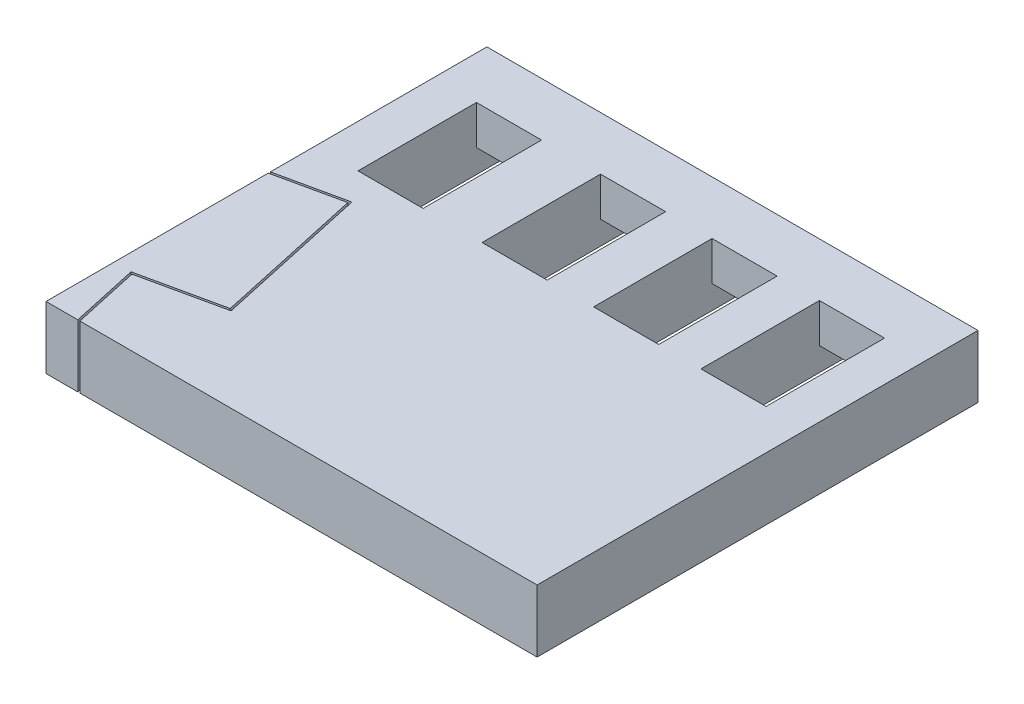
SolidWorks part; units mm, degrees
ref_plane "Front Plane" through (0, 0, 0) normal (0, 0, 1) x (1, 0, 0)
ref_plane "Top Plane" through (0, 0, 0) normal (0, 1, 0) x (1, 0, 0)
ref_plane "Right Plane" through (0, 0, 0) normal (1, 0, 0) x (0, 0, -1)
sketch "Sketch2" plane through (0, 0, 0) normal (0, 1, 0) x (1, 0, 0)
  line L0 (-9.37, 7.32) -> (73.63, 7.32) construction
  line L1 (73.63, 7.32) -> (76.4595, -28.3475) construction
  line L2 (76.4595, -28.3475) -> (60, -92.68) construction
  line L3 (60, -92.68) -> (0, -92.68) construction
  line L4 (0, -92.68) -> (-14.4952, -26.391) construction
  line L5 (-14.4952, -26.391) -> (-9.37, 7.32) construction
  line L6 (0, -92.68) -> (0, 7.32) construction
  line L7 (0, -92.68) -> (-39.3219, -55.4519) construction
  line L8 (-39.3219, -55.4519) -> (-24.668, -37.068) construction
  line L9 (-24.668, -37.068) -> (-14.4952, -26.391) construction
  line L10 (23.833, 7.32) -> (23.833, -92.68) construction
  line L11 (45.253, 7.32) -> (45.253, -92.68) construction
  line L12 (65.8765, 7.32) -> (65.8765, -69.7116) construction
  line L13 (75.6226, -17.7975) -> (-13.1887, -17.7975) construction
  line L14 (-9.3242, -50.0388) -> (70.9098, -50.0388) construction
  line L15 (-9.37, 7.32) -> (9.37, 7.32)
  line L16 (73.63, 7.32) -> (58.123, 7.32)
  line L17 (58.123, 7.32) -> (65.8765, 7.32)
  line L18 (35.883, 7.32) -> (54.623, 7.32)
  line L19 (14.463, 7.32) -> (33.203, 7.32)
  line L20 (21.0829, 0) -> (43.1082, 0) construction
  spline S0 degree 3 poles (-24.668, -37.068) (-25.0537, -36.7059) (-25.7619, -36.0411) (-26.7353, -35.1295) (-28.0424, -33.9071) (-29.2031, -32.8245) (-30.7142, -31.418) (-32.1196, -30.112) (-34.552, -27.8566) (-36.7318, -25.839) (-39.4542, -23.3171) (-41.6352, -21.2933) (-44.115, -18.9831) (-45.906, -17.309) (-47.5157, -15.8001) (-48.9606, -14.444) (-50.2857, -13.2006) (-51.3935, -12.1603) (-52.3511, -11.2593) (-53.3729, -10.2955) (-54.4927, -9.2355) (-55.8015, -7.9921) (-56.6965, -7.137) (-57.2305, -6.6269) knots 0 0 0 0 0.035582 0.065325 0.089678 0.15593 0.172056 0.228511 0.284969 0.395211 0.428397 0.534723 0.595442 0.656419 0.699627 0.743832 0.789646 0.821914 0.846336 0.87839 0.916737 0.950329 1 1 1 1 construction
  point P21 (0, 7.32)
  point P22 (65.8765, 0)
  point P28 (45.253, 7.32)
  point P31 (23.833, 7.32)
  point P32 (45.253, 0)
  point P33 (23.833, 0)
  dimension "D1" = 83
  dimension "D2" = 100
  dimension "D3" = 60
  dimension "D4" = 18.74
  dimension "D5" = 7.7535
  dimension "D6" = 10.55
  dimension "D7" = 18.74
  dimension "D8" = 18.74
  dimension "D9" = 3.5
  dimension "D10" = 2.68
ref_plane "Plane1" through (0, 0, -7.32) normal (0, 0, 1) x (1, 0, 0)
ref_plane "Plane2" through (0, 0, 92.68) normal (0, 0, -1) x (-1, 0, 0)
ref_plane "Plane jari tengah" through (23.833, 0, 0) normal (-1, 0, 0) x (0, 0, 1)
ref_plane "Plane telunjuk" through (0, 0, 0) normal (1, 0, 0) x (0, 0, -1)
ref_plane "Plane Jari MANIS" through (45.253, 0, 0) normal (-1, 0, 0) x (0, 0, 1)
ref_plane "Plane KELINGKING" through (65.8765, 0, 0) normal (-1, 0, 0) x (0, 0, 1)
sketch "Sketch8" plane through (0, 0, 92.68) normal (0, 0, -1) x (-1, 0, 0)
  line L0 (-60, 0) -> (0, 0) construction
  ellipse E0 centre (-30, 0) end of major axis (-60, 0) minor radius 14
  point P9 (-30, 0)
  dimension "D1" = 28
sketch "SK tengah" plane through (23.833, 0, 0) normal (-1, 0, 0) x (0, 0, 1)
  line L0 (-7.32, 9.9745) -> (0.9825, 14.5812) construction
  line L1 (0.9825, 14.5812) -> (92.68, 14.5812) construction
  line L2 (92.68, 14.5812) -> (92.68, -18.4188) construction
  line L3 (92.68, -18.4188) -> (-7.32, -18.4188) construction
  line L4 (-7.32, -18.4188) -> (-7.32, 9.9745) construction
  line L5 (25.1136, 0) -> (25.1136, 14.5812) construction
  line L6 (-7.32, 0) -> (92.68, 0) construction
  line L7 (25.1136, 0) -> (25.1136, -18.4188) construction
  line L8 (11.0531, -18.4188) -> (26.0531, -18.4188)
  line L9 (13.6136, 14.5812) -> (36.6136, 14.5812) construction
  point P3 (0, 0)
  point P21 (18.5531, -18.4188)
  point P23 (25.1136, 14.5812)
  dimension "D1" = 33
  dimension "D2" = 23
  dimension "D3" = 15
sketch "Sketch T tengah" plane through (23.833, 0, 0) normal (-1, 0, 0) x (0, 0, 1)
  line L1 (-7.32, -18.4188) -> (-7.32, 9.9745) construction
  line L3 (-7.72, -8.3628) -> (0.6719, -4.4495) construction
  spline S0 degree 1 poles (36.6136, 14.5812) (92.68, 13.701) knots 0 0 1 1
  spline S1 degree 3 poles (11.0531, -18.4188) (2.4609, -15.2512) (-3.4722, -11.6219) (-7.32, -8.1763) knots 0 0 0 0 1 1 1 1
  spline S2 degree 3 poles (26.0531, -18.4188) (48.3054, -13.7834) (72.3805, -31.2632) (92.68, -13.701) knots 0 0 0 0 1 1 1 1
  spline S3 degree 2 poles (13.6136, 14.5812) (4.5745, 14.3991) (-7.32, 5.7198) knots 0 0 0 1 1 1
  spline S4 degree 2 poles (11.0531, -18.4188) (19.1579, -19.8516) (26.9692, -18.2405) knots 0 0 0 1 1 1
  spline S5 degree 3 poles (13.6136, 14.5812) (23.8468, 14.7873) (29.5425, 14.6922) (37.7057, 14.5641) knots 0 0 0 0 1 1 1 1
sketch "Sketch T Telunjuk" plane through (0, 0, 0) normal (1, 0, 0) x (0, 0, -1)
  line L0 (-92.68, 14.5812) -> (-92.68, -18.4188) construction
  line L1 (-92.68, -18.4188) -> (7.32, -18.4188) construction
  line L2 (7.32, -18.4188) -> (7.32, 9.9745) construction
  line L3 (-0.9825, 14.5812) -> (-92.68, 14.5812) construction
  line L4 (7.32, 9.9745) -> (-0.9825, 14.5812) construction
  line L5 (-11.0531, -18.4188) -> (-26.0531, -18.4188) construction
  line L6 (-25.1136, 0) -> (-25.1136, -18.4188) construction
  line L7 (-13.6136, 14.5812) -> (-36.6136, 14.5812) construction
  line L8 (-25.1136, 0) -> (-25.1136, 14.5812) construction
  line L9 (-92.68, 14.5812) -> (-92.68, -18.4188) construction
  line L10 (-92.68, -18.4188) -> (7.32, -18.4188) construction
  line L11 (7.32, -18.4188) -> (7.32, 9.9745) construction
  line L12 (-0.9825, 14.5812) -> (-92.68, 14.5812) construction
  line L13 (7.32, 9.9745) -> (-0.9825, 14.5812) construction
  line L14 (-11.0531, -18.4188) -> (-26.0531, -18.4188)
  line L15 (-25.1136, 0) -> (-25.1136, -18.4188) construction
  line L16 (-13.6136, 14.5812) -> (-36.6136, 14.5812)
  line L17 (-25.1136, 0) -> (-25.1136, 14.5812) construction
  line L19 (-14, 6.5) -> (-18, 6.5) construction
  line L22 (-92.68, 2.3377) -> (-92.68, -9.5106) construction
  spline S0 degree 2 poles (-13.6136, 14.5812) (-1.7806, 13.7761) (7.32, 6.5) knots 0 0 0 1 1 1
  spline S1 degree 3 poles (-36.6136, 14.5812) (-55.7606, 12.6324) (-92.68, 8.8052) (-92.68, 0) knots 0 0 0 0 1 1 1 1
  spline S2 degree 2 poles (7.32, -9.651) (-1.1831, -15.409) (-11.0531, -18.4188) knots 0 0 0 1 1 1
  spline S3 degree 3 poles (-26.0531, -18.4188) (-34.8378, -16.2128) (-50.5034, -20.7443) (-75.8269, -26.8447) (-92.68, -20.3045) (-92.68, 0) knots 0 0 0 0 0.475651 0.575651 1 1 1 1
  spline S4 degree 2 poles (-11.0531, -18.4188) (-19.9341, -19.78) (-28.5243, -17.9627) knots 0 0 0 1 1 1
  spline S5 degree 2 poles (-36.6136, 14.5812) (-23.4423, 15.8073) (-10.4204, 14.2388) knots 0 0 0 1 1 1
  point P14 (0, 0)
sketch "Sketch T manis" plane through (45.253, 0, 0) normal (-1, 0, 0) x (0, 0, 1)
  line L0 (13.6136, 14.5812) -> (36.6136, 14.5812) construction
  line L1 (11.0531, -18.4188) -> (26.0531, -18.4188) construction
  line L2 (-7.32, 9.9745) -> (0.9825, 14.5812) construction
  line L3 (25.1136, 0) -> (25.1136, -18.4188) construction
  line L4 (25.1136, 0) -> (25.1136, 14.5812) construction
  line L5 (-7.32, -18.4188) -> (-7.32, 9.9745) construction
  line L6 (92.68, -18.4188) -> (-7.32, -18.4188) construction
  line L7 (92.68, 14.5812) -> (92.68, -18.4188) construction
  line L8 (0.9825, 14.5812) -> (92.68, 14.5812) construction
  line L9 (13.6136, 14.5812) -> (36.6136, 14.5812) construction
  line L10 (11.0531, -18.4188) -> (26.0531, -18.4188)
  line L11 (-7.32, 9.9745) -> (0.9825, 14.5812) construction
  line L12 (25.1136, 0) -> (25.1136, -18.4188)
  line L13 (25.1136, 0) -> (25.1136, 14.5812)
  line L14 (-7.32, -18.4188) -> (-7.32, 9.9745) construction
  line L15 (92.68, -18.4188) -> (-7.32, -18.4188) construction
  line L16 (92.68, 14.5812) -> (92.68, -18.4188) construction
  line L17 (0.9825, 14.5812) -> (92.68, 14.5812) construction
  line L18 (30.3671, 14.6142) -> (43.0115, 14.5474) construction
  spline S0 degree 2 poles (-7.32, -12.0108) (1.4272, -16.457) (11.0531, -18.4188) knots 0 0 0 1 1 1
  spline S1 degree 1 poles (11.0531, -18.4188) (26.0531, -18.4188) knots 0 0 1 1
  spline S2 degree 1 poles (11.0531, -18.4188) (26.0531, -18.4188) knots 0 0 1 1
  spline S3 degree 2 poles (-7.32, 5.7198) (2.2712, 12.9568) (13.6136, 14.5812) knots 0 0 0 1 1 1
  spline S4 degree 3 poles (36.6136, 14.5812) (55.2526, 14.4826) (74.0747, 13.0063) (92.68, 12.0554) knots 0 0 0 0 1 1 1 1
  spline S5 degree 3 poles (26.0531, -18.4188) (37.9494, -16.5166) (59.1128, -17.1776) (83.6124, -25.345) (92.68, -12.0554) knots 0 0 0 0 0.46971 1 1 1 1
  spline S6 degree 3 poles (26.0531, -18.4188) (48.3054, -13.7834) (72.3805, -31.2632) (92.68, -13.701) knots 0 0 0 0 1 1 1 1 construction
  spline S7 degree 2 poles (11.0531, -18.4188) (19.948, -19.5169) (28.6529, -18.034) knots 0 0 0 1 1 1
  spline S8 degree 3 poles (36.6136, 14.5812) (28.6207, 14.6235) (16.5345, 16.1804) (7.5854, 13.2859) knots 0 0 0 0 1 1 1 1
sketch "Sketch T kelingking" plane through (65.8765, 0, 0) normal (-1, 0, 0) x (0, 0, 1)
  line L0 (13.6136, 14.5812) -> (36.6136, 14.5812) construction
  line L1 (11.0531, -18.4188) -> (26.0531, -18.4188) construction
  line L2 (-7.32, 9.9745) -> (0.9825, 14.5812) construction
  line L3 (-7.32, -18.4188) -> (-7.32, 9.9745) construction
  line L4 (92.68, -18.4188) -> (-7.32, -18.4188) construction
  line L5 (92.68, 14.5812) -> (92.68, -18.4188) construction
  line L6 (0.9825, 14.5812) -> (92.68, 14.5812) construction
  line L7 (13.6136, 14.5812) -> (36.6136, 14.5812) construction
  line L8 (11.0531, -18.4188) -> (26.0531, -18.4188) construction
  line L9 (-7.32, 9.9745) -> (0.9825, 14.5812) construction
  line L10 (-7.32, -18.4188) -> (-7.32, 9.9745) construction
  line L11 (92.68, -18.4188) -> (-7.32, -18.4188) construction
  line L12 (92.68, 14.5812) -> (92.68, -18.4188) construction
  line L13 (0.9825, 14.5812) -> (92.68, 14.5812) construction
  line L18 (69.7116, 7.4976) -> (69.7116, -25.1077) construction
  spline S0 degree 3 poles (36.6136, 14.5812) (73.4975, 8.4898) (69.7116, 6.4971) (69.7116, 0) knots 0 0 0 0 1 1 1 1
  spline S1 degree 3 poles (26.0531, -18.4188) (63.7188, -17.6108) (69.7116, -7.3136) (69.7116, 0) knots 0 0 0 0 1 1 1 1
  spline S2 degree 2 poles (13.6136, 14.5812) (2.4977, 12.7323) (-7.32, 6.7519) knots 0 0 0 1 1 1
  spline S3 degree 2 poles (11.0531, -18.4188) (1.1233, -16.9603) (-7.32, -10.806) knots 0 0 0 1 1 1
  spline S5 degree 2 poles (26.0531, -18.4188) (16.4437, -19.8647) (7.1895, -17.6597) knots 0 0 0 1 1 1
  spline S6 degree 3 poles (36.6136, 14.5812) (27.5043, 16.0856) (18.5688, 15.8344) (9.8088, 13.8184) knots 0 0 0 0 1 1 1 1
sketch "SK kanan" plane through (0, 0, 0) normal (0, 1, 0) x (1, 0, 0)
  spline S0 degree 3 poles (60, -92.68) (61.5892, -84.604) (59.3724, -89.5882) (74.0327, -48.7356) (77.7794, -29.919) (74.0138, -8) knots 0 0 0 0 0.554349 0.654349 1 1 1 1
  spline S2 degree 2 poles (-9.37, 7.32) (-13.2861, -15.316) (-14.4952, -26.391) knots 0 0 0 1 1 1
  point P1 (76.9924, -6.4632)
  point P2 (78.6106, -6.4235)
  point P3 (70.8167, -57.8503)
  point P5 (68.7251, -63.4288)
  point P6 (62.2954, -83.7085)
  point P7 (0, 0)
ref_plane "Plane7" through (-39, 0, 39) normal (0.7071, 0, -0.7071) x (-0.7071, 0, -0.7071)
sketch3d "3DSketch2"
  line L0 (0, 0, 78) -> (-12.9801, 0, 78) construction
  line L1 (0, 0, 78) -> (0, 0, 63.3504) construction
  line L2 (0, 0, 0) -> (0, 0, 78) construction
  line L3 (0, 0, 78) -> (-36.5574, -17.6824, 46.0035) construction
  line L4 (-33.757, -19.037, 43.5525) -> (-39.3578, -16.3279, 48.4545) construction
  line L5 (0, 0, 78) -> (0, 8.4914, 78) construction
  line L6 (60, 0, 92.68) -> (0, 0, 92.68) construction
  line L7 (0, 0, 78) -> (-36.6074, 0, 41.3926) construction
  line L8 (-32.8, 0, 45.2) -> (-76.9196, 0, 1.0804) construction
  line L10 (-36.5574, 4.4756, 33.7582) -> (-36.5574, -39.8405, 58.2488) construction
  spline S0 degree 3 poles (0, 14.5812, 36.6136) (0, 12.6324, 55.7606) (0, 8.8052, 92.68) (0, 0, 92.68) knots 0 0 0 0 1 1 1 1 construction
  point P15 (-36.5574, -17.6824, 46.0035)
  point P18 (-36.5574, -17.6824, 46.0035)
  point P21 (-33.0219, -15.9723, 49.0979)
  dimension "D1" = 110
  dimension "D2" = 51.7
  dimension "D3" = 45
  dimension "D4" = 5
ref_plane "TOP PLANE JEMPOL" through (-34.1343, 16.5104, 29.8757) normal (0.7071, -0.342, -0.6189) x (-0.7071, -0.342, -0.6189)
ref_plane "RIGHT PLANE JEMPOL" through (0, -33.0209, 18.2485) normal (0, -0.8752, 0.4837) x (-0.7071, -0.342, -0.6189)
ref_plane "FRONT PLANE JEMPOL" through (-2.4231, -1.172, -2.1208) normal (0.7071, 0.342, 0.6189) x (0, -0.8752, 0.4837)
ref_plane "Plane19" through (4.7187, 2.2824, 4.13) normal (0.7071, 0.342, 0.6189) x (0, -0.8752, 0.4837)
ref_axis "Axis2" through (-36.5574, 29.8299, 19.7464) along (0, -0.8752, 0.4837)
ref_plane "Plane20" through (3.2697, 2.3447, 4.2428) normal (-0.5592, -0.401, -0.7256) x (0, -0.8752, 0.4837)
ref_axis "Axis3" through (-29.4156, 33.2843, 25.9972) along (0, -0.8752, 0.4837)
ref_plane "Plane21" through (8.8138, 6.3204, 11.4367) normal (-0.5592, -0.401, -0.7256) x (0, -0.8752, 0.4837)
sketch "Sketch17" plane through (0, -33.0209, 18.2485) normal (0, -0.8752, 0.4837) x (-0.7071, -0.342, -0.6189)
  circle A0 centre (-1.5733, -48.2733) radius 5
  circle A1 centre (-1.5733, -48.2733) radius 5.05
  dimension "D1" = 10
  dimension "D2" = 10.1
sketch "Sketch20" plane through (8.8138, 6.3204, 11.4367) normal (-0.5592, -0.401, -0.7256) x (0, -0.8752, 0.4837)
  circle A0 centre (37.7278, 46.113) radius 11.5
  dimension "D1" = 23
sketch "Sketch22" plane through (8.8138, 6.3204, 11.4367) normal (-0.5592, -0.401, -0.7256) x (0, -0.8752, 0.4837)
sketch3d "3DSketch3"
  line L0 (0, 0, 92.68) -> (-36.9816, -17.884, 60.1054) construction
  line L1 (-29.4156, -14.228, 52.2543) -> (-21.8497, -10.5721, 44.4031) construction
  line L2 (-29.4156, -14.228, 52.2543) -> (-35.2167, -4.3478, 51.2647) construction
  line L6 (-29.4156, -14.228, 52.2543) -> (-36.9816, -17.884, 60.1054) construction
  line L7 (-14.4952, 0, 26.391) -> (-21.8497, -10.5721, 44.4031) construction
  circle A0 centre (-29.4156, -14.228, 52.2543) radius 11.5 construction
  point P5 (-35.8464, -18.8395, 43.9098)
ref_plane "Plane22" through (0.0036, -0.0074, 0) normal (0.4353, -0.9003, 0.0001) x (-0.7054, -0.3411, -0.6213)
sketch "Sketch23" plane through (0.0036, -0.0074, 0) normal (0.4353, -0.9003, 0.0001) x (-0.7054, -0.3411, -0.6213)
  spline S0 degree 3 poles (-5.1583, -72.6191) (-40.7586, -74.8443) (-39.7755, -79.4448) (-57.5852, -72.6191) knots 0 0 0 0 1 1 1 1
sketch "Sketch24" plane through (0, 0, 0) normal (0, 0, 1) x (1, 0, 0)
  line L1 (-14.4952, 3.75) -> (79.8273, 3.75)
  line L2 (-14.4952, 3.75) -> (-14.4952, -8.25)
  line L3 (-14.4952, -8.25) -> (79.8273, -8.25)
  line L4 (79.8273, 3.75) -> (79.8273, -8.25)
  dimension "D1" = 12
  dimension "D2" = 8.25
extrude "Boss-Extrude1" add sketch "Sketch24" along normal blind 84.68 from offset 8
sketch "Sketch25" plane through (0, 0, 0) normal (0, 1, 0) x (1, 0, 0)
  line L0 (0, 0) -> (21.0829, 0) construction
  line L1 (-6.25, -13.6) -> (6.25, -13.6)
  line L2 (-6.25, -13.6) -> (-6.25, -45.65)
  line L3 (-6.25, -45.65) -> (6.25, -45.65)
  line L4 (6.25, -13.6) -> (6.25, -45.65)
  line L5 (-6.25, -13.6) -> (6.25, -45.65) construction
  line L6 (-6.25, -45.65) -> (6.25, -13.6) construction
  line L7 (0, -92.68) -> (0, 7.32) construction
  line L9 (17.583, -13.6) -> (30.083, -13.6)
  line L10 (17.583, -13.6) -> (17.583, -45.65)
  line L11 (17.583, -45.65) -> (30.083, -45.65)
  line L12 (30.083, -13.6) -> (30.083, -45.65)
  line L13 (17.583, -13.6) -> (30.083, -45.65) construction
  line L14 (17.583, -45.65) -> (30.083, -13.6) construction
  line L15 (39.003, -13.6) -> (51.503, -13.6)
  line L16 (39.003, -13.6) -> (39.003, -45.65)
  line L17 (39.003, -45.65) -> (51.503, -45.65)
  line L18 (51.503, -13.6) -> (51.503, -45.65)
  line L19 (39.003, -13.6) -> (51.503, -45.65) construction
  line L20 (39.003, -45.65) -> (51.503, -13.6) construction
  line L21 (23.833, 7.32) -> (23.833, -92.68) construction
  line L22 (45.253, 7.32) -> (45.253, -92.68) construction
  line L23 (21.0829, 0) -> (43.1082, 0) construction
  line L24 (43.1082, 0) -> (62.3488, 0) construction
  line L25 (65.8765, 7.32) -> (65.8765, -69.7116) construction
  line L26 (59.6265, -13.6) -> (72.1265, -13.6)
  line L27 (59.6265, -13.6) -> (59.6265, -45.65)
  line L28 (59.6265, -45.65) -> (72.1265, -45.65)
  line L29 (72.1265, -13.6) -> (72.1265, -45.65)
  line L30 (59.6265, -13.6) -> (72.1265, -45.65) construction
  line L31 (59.6265, -45.65) -> (72.1265, -13.6) construction
  line L33 (-6.25, -18.25) -> (6.25, -18.25)
  line L34 (-6.25, -18.25) -> (-6.25, -41)
  line L35 (-6.25, -41) -> (6.25, -41)
  line L36 (6.25, -18.25) -> (6.25, -41)
  line L37 (-6.25, -18.25) -> (6.25, -41) construction
  line L38 (-6.25, -41) -> (6.25, -18.25) construction
  line L39 (17.583, -18.25) -> (30.083, -18.25)
  line L40 (17.583, -18.25) -> (17.583, -41)
  line L41 (17.583, -41) -> (30.083, -41)
  line L42 (30.083, -18.25) -> (30.083, -41)
  line L43 (17.583, -18.25) -> (30.083, -41) construction
  line L44 (17.583, -41) -> (30.083, -18.25) construction
  line L45 (39.003, -18.25) -> (51.503, -18.25)
  line L46 (39.003, -18.25) -> (39.003, -41)
  line L47 (39.003, -41) -> (51.503, -41)
  line L48 (51.503, -18.25) -> (51.503, -41)
  line L49 (39.003, -18.25) -> (51.503, -41) construction
  line L50 (39.003, -41) -> (51.503, -18.25) construction
  line L51 (59.6265, -18.25) -> (72.1265, -18.25)
  line L52 (59.6265, -18.25) -> (59.6265, -41)
  line L53 (59.6265, -41) -> (72.1265, -41)
  line L54 (72.1265, -18.25) -> (72.1265, -41)
  line L55 (59.6265, -18.25) -> (72.1265, -41) construction
  line L56 (59.6265, -41) -> (72.1265, -18.25) construction
  point P0 (0, -29.625)
  point P5 (45.253, -29.625)
  point P15 (23.833, -29.625)
  point P22 (23.833, -29.625)
  point P32 (65.8765, -29.625)
  point P38 (0, -29.625)
  point P47 (45.253, -29.625)
  point P52 (65.8765, -29.625)
  dimension "D1" = 32.05
  dimension "D2" = 12.5
  dimension "D3" = 13.6
  dimension "D4" = 12.5
  dimension "D5" = 32.05
  dimension "D6" = 12.5
  dimension "D7" = 32.05
  dimension "D8" = 13.6
  dimension "D9" = 13.6
  dimension "D10" = 12.5
  dimension "D11" = 32.05
  dimension "D12" = 13.6
  dimension "D13" = 22.75
extrude "Cut-Extrude1" cut sketch "Sketch25" against normal through all both and the other way through all contours L33 L36 L35 L34 | L39 L42 L41 L40 | L45 L48 L47 L46 | L51 L54 L53 L52
extrude "Cut-Extrude2" cut sketch "Sketch25<5>" along normal blind 4.5 from surface contours L1 L4 L3 L2 | L9 L12 L11 L10 | L15 L18 L17 L16 | L26 L29 L28 L27 starting at face at (0, -8.25, 29.625)
sketch "Sketch25<5>" plane through (0, 0, 0) normal (0, 1, 0) x (1, 0, 0) same geometry as "Sketch25"
ref_plane "Plane23" through (-19.3413, 0, 4.2293) normal (0.9769, 0, -0.2136) x (-0.2136, 0, -0.9769)
ref_plane "Plane24" through (0, 0, 0) normal (0, -1, 0) x (-0.2136, 0, -0.9769)
sketch "Sketch27" plane through (-19.3413, 0, 4.2293) normal (0.9769, 0, -0.2136) x (-0.2136, 0, -0.9769)
  line L0 (-46.8919, 0) -> (-64.0315, 0) construction
  circle A0 centre (-60.5407, 0) radius 15
  point P2 (-59.8479, 0)
  point P6 (0, 0)
  dimension "D1" = 30
  dimension "D2" = 30
sketch "Sketch31" plane through (0, 0, 0) normal (0, -1, 0) x (-0.2136, 0, -0.9769)
  circle A0 centre (-60.5407, -19.7983) radius 8
  dimension "D1" = 16
sketch "Sketch30" plane through (0, 0, 0) normal (0, 1, 0) x (1, 0, 0)
  line L0 (-9.6129, -48.7187) -> (-1.7976, -47.0098) construction
  line L1 (-1.7976, -47.0098) -> (4.611, -76.3173)
  line L2 (4.611, -76.3173) -> (-3.2043, -78.0262) construction
  line L3 (0, -92.68) -> (-14.4952, -26.391) construction
  line L4 (4.611, -76.3173) -> (-11.0196, -79.7352)
  line L5 (-17.4282, -50.4277) -> (-22.2072, -28.5727)
  line L6 (-11.0196, -79.7352) -> (-6.135, -102.0732)
  line L9 (-1.7976, -47.0098) -> (-17.4282, -50.4277)
  circle A0 centre (-6.4086, -63.3725) radius 8 construction
extrude "Cut-Extrude-Thin1" cut sketch "Sketch30" against normal through all both and the other way through all thin thin type two direction wall 0.2 second wall 0.2
